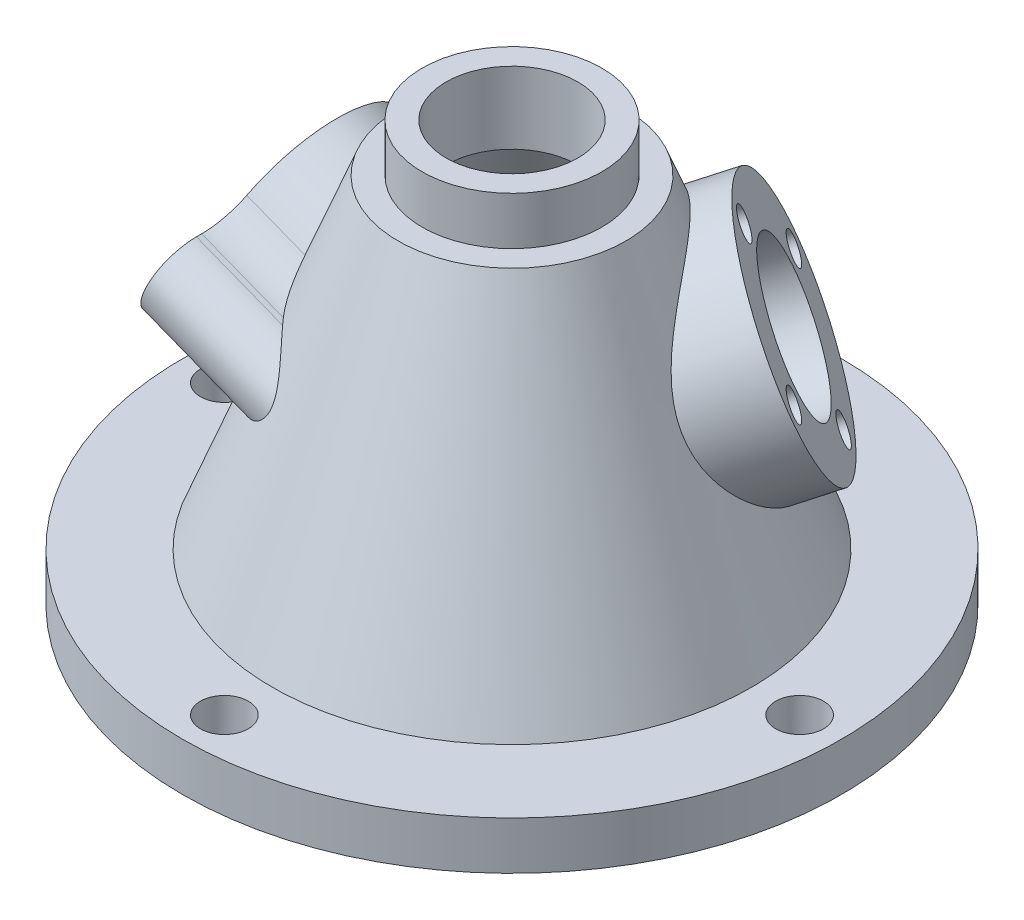
SolidWorks part; units mm, degrees
material "AISI 1020"
ref_plane "Front Plane" through (0, 0, 0) normal (0, 0, 1) x (1, 0, 0)
ref_plane "Top Plane" through (0, 0, 0) normal (0, 1, 0) x (1, 0, 0)
ref_plane "Right Plane" through (0, 0, 0) normal (1, 0, 0) x (0, 0, -1)
sketch "Sketch1" plane through (0, 0, 0) normal (0, 0, 1) x (1, 0, 0)
  line L0 (0, 0) -> (31618.6061, 0) construction
  line L1 (0, 0) -> (0, 31618.6061) construction
  line L2 (7.5, 35) -> (7.5, 31)
  line L3 (7.5, 31) -> (9.5, 31)
  line L4 (9.5, 31) -> (20, 4)
  line L5 (20, 4) -> (27.5, 4)
  line L6 (27.5, 4) -> (27.5, 0)
  line L7 (27.5, 0) -> (19.4096, 0)
  line L8 (19.4096, 0) -> (8.1319, 29)
  line L9 (8.1319, 29) -> (5.5, 29)
  line L10 (5.5, 29) -> (5.5, 35)
  line L11 (5.5, 35) -> (7.5, 35)
  point P7 (8.18, 29.3178)
  dimension "D1" = 15
  dimension "D2" = 2
  dimension "D3" = 19
  dimension "D4" = 2
  dimension "D5" = 4
  dimension "D6" = 2
  dimension "D7" = 55
  dimension "D8" = 40
  dimension "D9" = 4
  dimension "D10" = 35
revolve "Revolve1" add sketch "Sketch1" angle 360 about L1
sketch "Sketch2" plane through (0, 35, 0) normal (0, 1, 0) x (1, 0, 0)
  line L0 (0, 0) -> (0, 50000) construction
ref_plane "Plane3" through (-11.8453, 4.6183, 0) normal (0.9317, -0.3633, 0) x (0, 0, -1)
ref_plane "Plane4" through (-22.0939, 8.6141, 0) normal (0.9317, -0.3633, 0) x (0, 0, -1)
sketch "Sketch5" plane through (-22.0939, 8.6141, 0) normal (0.9317, -0.3633, 0) x (0, 0, -1)
  line L0 (0, 0) -> (0, 50000) construction
  line L1 (-200000, 32.6092) -> (250000, 32.6092) construction
  line L2 (10, 9.3592) -> (9.5623, 9.3592)
  line L3 (-10, 9.3592) -> (-9.5623, 9.3592)
  line L4 (-10, 15.8592) -> (-9.5623, 15.8592)
  line L5 (10, 15.8592) -> (9.5623, 15.8592)
  arc A0 (-6.3749, 7.7759) -> (6.3749, 7.7759) centre (0, 12.6092) ccw
  arc A1 (-10, 15.8592) -> (-10, 9.3592) centre (-10, 12.6092) ccw
  arc A2 (10, 15.8592) -> (10, 9.3592) centre (10, 12.6092) cw
  arc A3 (6.3749, 17.4425) -> (-6.3749, 17.4425) centre (0, 12.6092) ccw
  arc A4 (6.3749, 7.7759) -> (9.5623, 9.3592) centre (9.5623, 5.3592) cw
  arc A5 (-9.5623, 9.3592) -> (-6.3749, 7.7759) centre (-9.5623, 5.3592) cw
  arc A6 (-9.5623, 15.8592) -> (-6.3749, 17.4425) centre (-9.5623, 19.8592) ccw
  arc A7 (9.5623, 15.8592) -> (6.3749, 17.4425) centre (9.5623, 19.8592) cw
  circle A8 centre (0, 12.6092) radius 7
  circle A9 centre (-10, 12.6092) radius 1.25
  circle A10 centre (10, 12.6092) radius 1.25
  point P24 (7.3101, 15.8592)
  dimension "D1" = 16
  dimension "D2" = 6.5
  dimension "D5" = 4
  dimension "D6" = 2.5
  dimension "D7" = 14
  dimension "D3" = 20
  dimension "D4" = 20
extrude "Boss-Extrude6" add sketch "Sketch5" along normal up to next contours A8 L0 | L0 A8 | L0 A0 A4 L2 A2 L5 A7 A3 A8 A10 | A10 | A0 L0 A8 A3 A6 L4 A1 L3 A5 A9 | A9 region at (-17.5136, 20.3619, 7.6595) region at (-17.5136, 20.3619, -7.6595) region at (-17.5136, 20.3619, 2.9709) region at (-17.5136, 20.3619, -2.9709) region at (-17.5136, 20.3619, 10) region at (-17.5136, 20.3619, -10)
extrude "Cut-Extrude3" cut sketch "Sketch5<10>" along normal up to next contours L0 A8 | A8 L0 | A9 | A10 region at (-17.5136, 20.3619, 2.9709) region at (-17.5136, 20.3619, -2.9709) region at (-17.5136, 20.3619, 10) region at (-17.5136, 20.3619, -10)
sketch "Sketch5<10>" plane through (-22.0939, 8.6141, 0) normal (0.9317, -0.3633, 0) x (0, 0, -1) same geometry as "Sketch5"
sketch "Sketch7" plane through (0, 35, 0) normal (0, 1, 0) x (1, 0, 0)
  line L0 (0, 0) -> (50000, 0) construction
  line L4 (0, 0) -> (-35355.3391, 35355.3391) construction
  dimension "D1" = 45
sketch "Sketch8" plane through (0, 35, 0) normal (0, 1, 0) x (1, 0, 0)
  line L0 (0, 0) -> (-50000, 0) construction
  line L1 (0, 0) -> (-35355.3391, 35355.3391) construction
  dimension "D1" = 45
ref_plane "Plane5" through (0, 0, 0) normal (-0.7071, 0, 0.7071) x (0.7071, 0, 0.7071)
ref_plane "Plane7" through (8.4393, 4.7013, -8.4393) normal (-0.6579, -0.3665, 0.6579) x (-0.7071, 0, -0.7071)
ref_plane "Plane8" through (15.0183, 8.3663, -15.0183) normal (-0.6579, -0.3665, 0.6579) x (-0.7071, 0, -0.7071)
sketch "Sketch9" plane through (15.0183, 8.3663, -15.0183) normal (-0.6579, -0.3665, 0.6579) x (-0.7071, 0, -0.7071)
  line L0 (0, 0) -> (0, -50000) construction
  line L1 (-200000, -32.5646) -> (250000, -32.5646) construction
  circle A0 centre (0, -12.5646) radius 6
  circle A1 centre (0, -12.5646) radius 10
  circle A2 centre (0, -12.5646) radius 8 construction
  circle A3 centre (8, -12.5646) radius 1.25
  circle A4 centre (0, -20.5646) radius 1.25
  circle A5 centre (-8, -12.5646) radius 1.25
  circle A6 centre (0, -4.5646) radius 1.25
  point P20 (0, -12.5646)
  dimension "D1" = 12
  dimension "D2" = 16
  dimension "D3" = 20
  dimension "D5" = 2.5
  dimension "D4" = 20
  dimension "D6" = 4
extrude "Boss-Extrude8" add sketch "Sketch9" along normal up to next contours A0 | A1 A6 A5 A4 A3 A0 | A5 | A4 | A6 | A3 region at (11.7622, 20.0567, -11.7622) region at (18.6332, 20.0567, -4.8911) region at (6.1053, 20.0567, -17.419) region at (9.6889, 27.5, -9.6889) region at (17.419, 20.0567, -6.1053) region at (13.8354, 12.6133, -13.8354)
extrude "Cut-Extrude5" cut sketch "Sketch9<5>" along normal up to next contours A0 | A5 | A4 | A3 | A6 region at (11.7622, 20.0567, -11.7622) region at (6.1053, 20.0567, -17.419) region at (9.6889, 27.5, -9.6889) region at (17.419, 20.0567, -6.1053) region at (13.8354, 12.6133, -13.8354)
sketch "Sketch9<5>" plane through (15.0183, 8.3663, -15.0183) normal (-0.6579, -0.3665, 0.6579) x (-0.7071, 0, -0.7071) same geometry as "Sketch9"
sketch "Sketch13" plane through (0, 0, 0) normal (0, 1, 0) x (1, 0, 0)
  circle A0 centre (0, 0) radius 24 construction
  circle A1 centre (-24, 0) radius 2
  circle A2 centre (0, 24) radius 2
  circle A3 centre (24, 0) radius 2
  circle A4 centre (0, -24) radius 2
  point P6 (0, 0)
  point P13 (0, 0)
  dimension "D1" = 48
  dimension "D2" = 4
  dimension "D3" = 4
extrude "Cut-Extrude7" cut sketch "Sketch13" along normal blind 10 contours A1 | A1 | A2 | A3 | A4 region at (-24, 0, 0)
